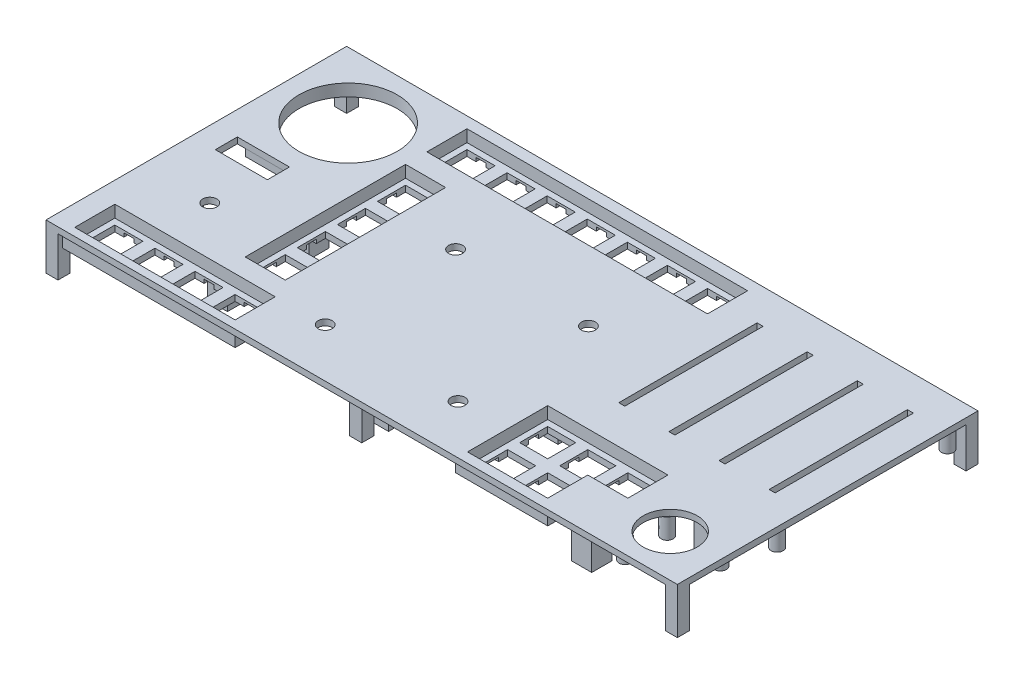
SolidWorks part; units mm, degrees
ref_plane "Front Plane" through (0, 0, 0) normal (0, 0, 1) x (1, 0, 0)
ref_plane "Top Plane" through (0, 0, 0) normal (0, 1, 0) x (1, 0, 0)
ref_plane "Right Plane" through (0, 0, 0) normal (1, 0, 0) x (0, 0, -1)
sketch "Sketch1" plane through (0, 0, 0) normal (0, 1, 0) x (1, 0, 0)
  line L1 (0, 0) -> (315, 0)
  line L2 (0, 0) -> (0, 150)
  line L3 (0, 150) -> (315, 150)
  line L4 (315, 0) -> (315, 150)
  line L5 (157.5, 150) -> (157.5, 0) construction
  line L6 (0, 75) -> (315, 75) construction
  line L7 (11.8793, 83.5932) -> (37.8793, 83.5932)
  line L8 (11.8793, 83.5932) -> (11.8793, 72.5932)
  line L9 (11.8793, 72.5932) -> (37.8793, 72.5932)
  line L10 (37.8793, 83.5932) -> (37.8793, 72.5932)
  line L11 (24.8793, 72.5932) -> (24.8793, 83.5932) construction
  line L12 (11.8793, 78.0932) -> (37.8793, 78.0932) construction
  line L17 (114.9071, 89.45) -> (181.1755, 89.45) construction
  line L18 (65.6251, 144.4154) -> (205.6251, 144.4154)
  line L42 (260.2509, 144.4154) -> (285.2509, 144.4154)
  line L43 (234.1707, 144.4154) -> (259.1707, 144.4154)
  line L44 (234.1707, 144.4154) -> (234.1707, 52.4154)
  line L45 (234.1707, 52.4154) -> (259.1707, 52.4154)
  line L46 (259.1707, 144.4154) -> (259.1707, 52.4154)
  line L47 (246.6707, 52.4154) -> (246.6707, 144.4154) construction
  line L48 (234.1707, 98.4154) -> (259.1707, 98.4154) construction
  line L49 (260.2509, 144.4154) -> (260.2509, 52.4154)
  line L50 (260.2509, 52.4154) -> (285.2509, 52.4154)
  line L51 (285.2509, 144.4154) -> (285.2509, 52.4154)
  line L52 (287.1734, 144.4154) -> (312.1734, 144.4154)
  line L53 (287.1734, 144.4154) -> (287.1734, 52.4154)
  line L54 (287.1734, 52.4154) -> (312.1734, 52.4154)
  line L55 (312.1734, 144.4154) -> (312.1734, 52.4154)
  line L72 (65.6251, 144.4154) -> (65.6251, 124.4154)
  line L73 (65.6251, 124.4154) -> (205.6251, 124.4154)
  line L74 (205.6251, 144.4154) -> (205.6251, 124.4154)
  line L75 (135.6251, 124.4154) -> (135.6251, 144.4154) construction
  line L76 (65.6251, 134.4154) -> (205.6251, 134.4154) construction
  line L81 (65.688, 113.6965) -> (85.688, 113.6965)
  line L82 (65.688, 113.6965) -> (65.688, 33.6965)
  line L83 (10.3843, 23.9694) -> (90.3843, 23.9694)
  line L84 (10.3843, 23.9694) -> (10.3843, 3.9694)
  line L85 (10.3843, 3.9694) -> (90.3843, 3.9694)
  line L86 (90.3843, 23.9694) -> (90.3843, 3.9694)
  line L87 (50.3843, 3.9694) -> (50.3843, 23.9694) construction
  line L88 (10.3843, 13.9694) -> (90.3843, 13.9694) construction
  line L89 (65.688, 33.6965) -> (85.688, 33.6965)
  line L90 (85.688, 113.6965) -> (85.688, 33.6965)
  line L91 (75.688, 33.6965) -> (75.688, 113.6965) construction
  line L92 (65.688, 73.6965) -> (85.688, 73.6965) construction
  line L93 (205.3895, 44.9232) -> (245.3895, 44.9232)
  line L94 (205.3895, 44.9232) -> (205.3895, 4.9232)
  line L95 (205.3895, 4.9232) -> (245.3895, 4.9232)
  line L96 (245.3895, 44.9232) -> (245.3895, 4.9232)
  line L97 (225.3895, 4.9232) -> (225.3895, 44.9232) construction
  line L98 (205.3895, 24.9232) -> (245.3895, 24.9232) construction
  line L99 (245.3895, 44.9232) -> (265.3895, 44.9232)
  line L100 (245.3895, 44.9232) -> (245.3895, 24.9232)
  line L101 (245.3895, 24.9232) -> (265.3895, 24.9232)
  line L102 (265.3895, 44.9232) -> (265.3895, 24.9232)
  line L103 (255.3895, 24.9232) -> (255.3895, 44.9232) construction
  line L104 (245.3895, 34.9232) -> (265.3895, 34.9232) construction
  line L105 (181.1755, 89.45) -> (181.1755, 24.3783) construction
  line L106 (181.1755, 24.3783) -> (114.9071, 24.3783) construction
  line L107 (33.5208, 117.195) -> (33.5208, 48.1962) construction
  line L109 (273.3018, 34.1392) -> (307.3018, 34.1392)
  line L110 (273.3018, 34.1392) -> (273.3018, 8.1392)
  line L111 (273.3018, 8.1392) -> (307.3018, 8.1392)
  line L112 (307.3018, 34.1392) -> (307.3018, 8.1392)
  line L113 (290.3018, 8.1392) -> (290.3018, 34.1392) construction
  line L114 (273.3018, 21.1392) -> (307.3018, 21.1392) construction
  line L115 (117.5413, 65.9142) -> (178.5413, 65.9142)
  line L116 (117.5413, 65.9142) -> (117.5413, 47.9142)
  line L117 (117.5413, 47.9142) -> (178.5413, 47.9142)
  line L118 (178.5413, 65.9142) -> (178.5413, 47.9142)
  line L119 (148.0413, 47.9142) -> (148.0413, 65.9142) construction
  line L120 (117.5413, 56.9142) -> (178.5413, 56.9142) construction
  line L121 (5.8793, 85.7294) -> (45.8793, 85.7294)
  line L122 (5.8793, 85.7294) -> (5.8793, 70.457)
  line L123 (5.8793, 70.457) -> (45.8793, 70.457)
  line L124 (45.8793, 85.7294) -> (45.8793, 70.457)
  line L125 (25.8793, 70.457) -> (25.8793, 85.7294) construction
  line L126 (5.8793, 78.0932) -> (45.8793, 78.0932) construction
  circle A0 centre (33.5208, 117.195) radius 27.5
  circle A1 centre (33.5208, 48.1962) radius 20
  circle A2 centre (114.9071, 24.3783) radius 20
  circle A3 centre (114.9071, 89.45) radius 20
  circle A4 centre (181.1755, 24.3783) radius 20
  circle A5 centre (181.1755, 89.45) radius 20
  point P38 (148.0413, 56.9142)
  point P42 (148.0413, 89.45)
  point P56 (181.1755, 56.9142)
  point P57 (25.8793, 78.0932)
  point P195 (24.8793, 78.0932)
  point P224 (290.3018, 21.1392)
  point P252 (246.6707, 98.4154)
  point P259 (225.3895, 24.9232)
  point P417 (255.3895, 34.9232)
  point P438 (75.688, 73.6965)
  point P456 (157.5, 75)
  point P559 (50.3843, 13.9694)
  point P704 (135.6251, 134.4154)
  dimension "D3" = 55
  dimension "D6" = 40
  dimension "D1" = 150
  dimension "D2" = 315
  dimension "D4" = 26
  dimension "D5" = 11
  dimension "D7" = 20
  dimension "D8" = 140
  dimension "D9" = 25
  dimension "D10" = 92
  dimension "D11" = 20
  dimension "D12" = 80
  dimension "D13" = 20
  dimension "D14" = 80
  dimension "D15" = 40
  dimension "D16" = 40
  dimension "D17" = 20
  dimension "D18" = 34
  dimension "D19" = 26
  dimension "D20" = 61
  dimension "D21" = 18
  dimension "D22" = 6
  dimension "D23" = 8
  dimension "D24" = 25
  dimension "D25" = 25
sketch "Sketch2" plane through (0, 0, 0) normal (0, 1, 0) x (1, 0, 0)
  line L1 (0, 0) -> (315, 0)
  line L2 (0, 0) -> (0, 150)
  line L3 (0, 150) -> (315, 150)
  line L4 (315, 0) -> (315, 150)
  line L5 (157.5, 150) -> (157.5, 0) construction
  line L6 (0, 75) -> (315, 75) construction
  point P0 (157.5, 75)
extrude "Boss-Extrude1" add sketch "Sketch2" along normal blind 3
sketch "Sketch3" [suppressed] plane through (0, 0, 0) normal (0, 1, 0) x (1, 0, 0)
  line L0 (114.9071, 89.45) -> (114.9071, 81.45) construction
  line L1 (113.1571, 82.7) -> (116.6571, 82.7)
  line L2 (113.1571, 82.7) -> (113.1571, 80.2)
  line L3 (113.1571, 80.2) -> (116.6571, 80.2)
  line L4 (116.6571, 82.7) -> (116.6571, 80.2)
  line L5 (114.9071, 80.2) -> (114.9071, 82.7) construction
  line L6 (113.1571, 81.45) -> (116.6571, 81.45) construction
  line L7 (179.4255, 82.7) -> (182.9255, 82.7)
  line L8 (179.4255, 82.7) -> (179.4255, 80.2)
  line L9 (179.4255, 80.2) -> (182.9255, 80.2)
  line L10 (182.9255, 82.7) -> (182.9255, 80.2)
  line L11 (181.1755, 80.2) -> (181.1755, 82.7) construction
  line L12 (179.4255, 81.45) -> (182.9255, 81.45) construction
  line L13 (179.4255, 17.6283) -> (182.9255, 17.6283)
  line L14 (179.4255, 17.6283) -> (179.4255, 15.1283)
  line L15 (179.4255, 15.1283) -> (182.9255, 15.1283)
  line L16 (182.9255, 17.6283) -> (182.9255, 15.1283)
  line L17 (181.1755, 15.1283) -> (181.1755, 17.6283) construction
  line L18 (179.4255, 16.3783) -> (182.9255, 16.3783) construction
  line L19 (113.1571, 17.6283) -> (116.6571, 17.6283)
  line L20 (113.1571, 17.6283) -> (113.1571, 15.1283)
  line L21 (113.1571, 15.1283) -> (116.6571, 15.1283)
  line L22 (116.6571, 17.6283) -> (116.6571, 15.1283)
  line L23 (114.9071, 15.1283) -> (114.9071, 17.6283) construction
  line L24 (113.1571, 16.3783) -> (116.6571, 16.3783) construction
  line L25 (31.7708, 41.4462) -> (35.2708, 41.4462)
  line L26 (31.7708, 41.4462) -> (31.7708, 38.9462)
  line L27 (31.7708, 38.9462) -> (35.2708, 38.9462)
  line L28 (35.2708, 41.4462) -> (35.2708, 38.9462)
  line L29 (33.5208, 38.9462) -> (33.5208, 41.4462) construction
  line L30 (31.7708, 40.1962) -> (35.2708, 40.1962) construction
  line L31 (181.1755, 89.45) -> (181.1755, 82.7) construction
  line L32 (114.9071, 24.3783) -> (114.9071, 17.6283) construction
  line L33 (181.1755, 24.3783) -> (181.1755, 17.6283) construction
  line L34 (33.5208, 48.1962) -> (33.5208, 41.4462) construction
  circle A0 centre (114.9071, 89.45) radius 3.6
  circle A1 centre (181.1755, 89.45) radius 3.6
  circle A2 centre (181.1755, 24.3783) radius 3.6
  circle A3 centre (114.9071, 24.3783) radius 3.6
  circle A4 centre (33.5208, 48.1962) radius 3.6
  point P15 (114.9071, 81.45)
  point P19 (181.1755, 81.45)
  point P23 (181.1755, 16.3783)
  point P27 (114.9071, 16.3783)
  point P31 (33.5208, 40.1962)
  dimension "D1" = 7.2
  dimension "D2" = 8
  dimension "D3" = 8
  dimension "D4" = 8
  dimension "D5" = 8
  dimension "D6" = 3.5
  dimension "D7" = 2.5
  dimension "D8" = 8
extrude "rotatry_potentiameter_hole" [suppressed] cut sketch "Sketch3" along normal blind 3
sketch "Sketch4" [suppressed] plane through (0, 0, 0) normal (0, 1, 0) x (1, 0, 0)
  line L0 (114.9071, 12.8783) -> (114.9071, 14.8783)
  line L1 (114.9071, 33.8783) -> (114.9071, 35.8783)
  line L2 (181.1755, 12.8783) -> (181.1755, 14.8783)
  line L3 (181.1755, 33.8783) -> (181.1755, 35.8783)
  line L4 (114.9071, 79.95) -> (114.9071, 77.95)
  line L5 (114.9071, 100.95) -> (114.9071, 98.95)
  line L6 (114.9071, 24.3783) -> (114.9071, 89.45) construction
  line L7 (181.1755, 77.95) -> (181.1755, 79.95)
  line L8 (181.1755, 98.95) -> (181.1755, 100.95)
  line L9 (181.1755, 89.45) -> (181.1755, 24.3783) construction
  line L10 (33.5208, 36.6962) -> (33.5208, 38.6962)
  line L11 (33.5208, 57.6962) -> (33.5208, 59.6962)
  line L12 (33.5208, 117.195) -> (33.5208, 48.1962) construction
  arc A0 (114.9071, 14.8783) -> (114.9071, 33.8783) centre (114.9071, 24.3783) cw
  arc A1 (114.9071, 12.8783) -> (114.9071, 35.8783) centre (114.9071, 24.3783) cw
  arc A2 (181.1755, 14.8783) -> (181.1755, 33.8783) centre (181.1755, 24.3783) cw
  arc A3 (181.1755, 12.8783) -> (181.1755, 35.8783) centre (181.1755, 24.3783) cw
  arc A4 (114.9071, 77.95) -> (114.9071, 100.95) centre (114.9071, 89.45) cw
  arc A5 (114.9071, 79.95) -> (114.9071, 98.95) centre (114.9071, 89.45) cw
  arc A6 (181.1755, 79.95) -> (181.1755, 98.95) centre (181.1755, 89.45) cw
  arc A7 (181.1755, 77.95) -> (181.1755, 100.95) centre (181.1755, 89.45) cw
  arc A8 (33.5208, 38.6962) -> (33.5208, 57.6962) centre (33.5208, 48.1962) cw
  arc A9 (33.5208, 36.6962) -> (33.5208, 59.6962) centre (33.5208, 48.1962) cw
  dimension "D1" = 9.5
  dimension "D3" = 9.5
  dimension "D6" = 9.5
  dimension "D7" = 9.5
  dimension "D9" = 9.5
  dimension "D2" = 2
  dimension "D4" = 2
  dimension "D5" = 2
  dimension "D8" = 2
  dimension "D10" = 2
extrude "Boss-Extrude2" [suppressed] add sketch "Sketch4" against normal blind 5
sketch "Sketch28" plane through (0, 0, 0) normal (0, 1, 0) x (1, 0, 0)
  circle A0 centre (114.9071, 89.45) radius 3.5
  circle A1 centre (181.1755, 89.45) radius 3.5
  circle A2 centre (181.1755, 24.3783) radius 3.5
  circle A3 centre (114.9071, 24.3783) radius 3.5
  circle A4 centre (33.5208, 48.1962) radius 3.5
  dimension "D1" = 7
extrude "Cut-Extrude15" cut sketch "Sketch28" along normal blind 10
sketch "Sketch29" plane through (0, 0, 0) normal (0, 1, 0) x (1, 0, 0)
  line L0 (108.5671, 80.95) -> (125.5671, 80.95) construction
  line L1 (114.9071, 89.45) -> (114.9071, 80.95) construction
  line L2 (173.7538, 79.9853) -> (190.7538, 79.9853) construction
  line L3 (123.0671, 83.45) -> (128.0671, 83.45)
  line L4 (123.0671, 83.45) -> (123.0671, 78.45)
  line L5 (123.0671, 78.45) -> (128.0671, 78.45)
  line L6 (128.0671, 83.45) -> (128.0671, 78.45)
  line L7 (125.5671, 78.45) -> (125.5671, 83.45) construction
  line L8 (123.0671, 80.95) -> (128.0671, 80.95) construction
  line L9 (106.0671, 83.45) -> (111.0671, 83.45)
  line L10 (106.0671, 83.45) -> (106.0671, 78.45)
  line L11 (106.0671, 78.45) -> (111.0671, 78.45)
  line L12 (111.0671, 83.45) -> (111.0671, 78.45)
  line L13 (108.5671, 78.45) -> (108.5671, 83.45) construction
  line L14 (106.0671, 80.95) -> (111.0671, 80.95) construction
  line L15 (180.0938, 88.4853) -> (180.0938, 79.9853) construction
  line L16 (188.2538, 82.4853) -> (193.2538, 82.4853)
  line L17 (188.2538, 82.4853) -> (188.2538, 77.4853)
  line L18 (188.2538, 77.4853) -> (193.2538, 77.4853)
  line L19 (193.2538, 82.4853) -> (193.2538, 77.4853)
  line L20 (190.7538, 77.4853) -> (190.7538, 82.4853) construction
  line L21 (188.2538, 79.9853) -> (193.2538, 79.9853) construction
  line L22 (171.2538, 82.4853) -> (176.2538, 82.4853)
  line L23 (171.2538, 82.4853) -> (171.2538, 77.4853)
  line L24 (171.2538, 77.4853) -> (176.2538, 77.4853)
  line L25 (176.2538, 82.4853) -> (176.2538, 77.4853)
  line L26 (173.7538, 77.4853) -> (173.7538, 82.4853) construction
  line L27 (171.2538, 79.9853) -> (176.2538, 79.9853) construction
  line L28 (174.8355, 15.8783) -> (191.8355, 15.8783) construction
  line L29 (181.1755, 24.3783) -> (181.1755, 15.8783) construction
  line L30 (189.3355, 18.3783) -> (194.3355, 18.3783)
  line L31 (189.3355, 18.3783) -> (189.3355, 13.3783)
  line L32 (189.3355, 13.3783) -> (194.3355, 13.3783)
  line L33 (194.3355, 18.3783) -> (194.3355, 13.3783)
  line L34 (191.8355, 13.3783) -> (191.8355, 18.3783) construction
  line L35 (189.3355, 15.8783) -> (194.3355, 15.8783) construction
  line L36 (172.3355, 18.3783) -> (177.3355, 18.3783)
  line L37 (172.3355, 18.3783) -> (172.3355, 13.3783)
  line L38 (172.3355, 13.3783) -> (177.3355, 13.3783)
  line L39 (177.3355, 18.3783) -> (177.3355, 13.3783)
  line L40 (174.8355, 13.3783) -> (174.8355, 18.3783) construction
  line L41 (172.3355, 15.8783) -> (177.3355, 15.8783) construction
  line L42 (108.5671, 15.8783) -> (125.5671, 15.8783) construction
  line L43 (114.9071, 24.3783) -> (114.9071, 15.8783) construction
  line L44 (123.0671, 18.3783) -> (128.0671, 18.3783)
  line L45 (123.0671, 18.3783) -> (123.0671, 13.3783)
  line L46 (123.0671, 13.3783) -> (128.0671, 13.3783)
  line L47 (128.0671, 18.3783) -> (128.0671, 13.3783)
  line L48 (125.5671, 13.3783) -> (125.5671, 18.3783) construction
  line L49 (123.0671, 15.8783) -> (128.0671, 15.8783) construction
  line L50 (106.0671, 18.3783) -> (111.0671, 18.3783)
  line L51 (106.0671, 18.3783) -> (106.0671, 13.3783)
  line L52 (106.0671, 13.3783) -> (111.0671, 13.3783)
  line L53 (111.0671, 18.3783) -> (111.0671, 13.3783)
  line L54 (108.5671, 13.3783) -> (108.5671, 18.3783) construction
  line L55 (106.0671, 15.8783) -> (111.0671, 15.8783) construction
  line L56 (27.1808, 39.6962) -> (44.1808, 39.6962) construction
  line L57 (33.5208, 48.1962) -> (33.5208, 39.6962) construction
  line L58 (41.6808, 42.1962) -> (46.6808, 42.1962)
  line L59 (41.6808, 42.1962) -> (41.6808, 37.1962)
  line L60 (41.6808, 37.1962) -> (46.6808, 37.1962)
  line L61 (46.6808, 42.1962) -> (46.6808, 37.1962)
  line L62 (44.1808, 37.1962) -> (44.1808, 42.1962) construction
  line L63 (41.6808, 39.6962) -> (46.6808, 39.6962) construction
  line L64 (24.6808, 42.1962) -> (29.6808, 42.1962)
  line L65 (24.6808, 42.1962) -> (24.6808, 37.1962)
  line L66 (24.6808, 37.1962) -> (29.6808, 37.1962)
  line L67 (29.6808, 42.1962) -> (29.6808, 37.1962)
  line L68 (27.1808, 37.1962) -> (27.1808, 42.1962) construction
  line L69 (24.6808, 39.6962) -> (29.6808, 39.6962) construction
  circle A0 centre (108.5671, 80.95) radius 1.6
  circle A1 centre (125.5671, 80.95) radius 1.6
  circle A2 centre (173.7538, 79.9853) radius 1.6
  circle A3 centre (190.7538, 79.9853) radius 1.6
  circle A4 centre (174.8355, 15.8783) radius 1.6
  circle A5 centre (191.8355, 15.8783) radius 1.6
  circle A6 centre (108.5671, 15.8783) radius 1.6
  circle A7 centre (125.5671, 15.8783) radius 1.6
  circle A8 centre (27.1808, 39.6962) radius 1.6
  circle A9 centre (44.1808, 39.6962) radius 1.6
  dimension "D4" = 3.2
  dimension "D5" = 3.2
  dimension "D12" = 3.2
  dimension "D13" = 3.2
  dimension "D20" = 3.2
  dimension "D21" = 3.2
  dimension "D28" = 3.2
  dimension "D29" = 3.2
  dimension "D36" = 3.2
  dimension "D37" = 3.2
  dimension "D1" = 8.5
  dimension "D2" = 6.34
  dimension "D3" = 17
  dimension "D6" = 5
  dimension "D7" = 5
  dimension "D8" = 5
  dimension "D9" = 5
  dimension "D10" = 6.34
  dimension "D11" = 17
  dimension "D14" = 5
  dimension "D15" = 5
  dimension "D16" = 5
  dimension "D17" = 5
  dimension "D18" = 6.34
  dimension "D19" = 17
  dimension "D22" = 5
  dimension "D23" = 5
  dimension "D24" = 5
  dimension "D25" = 5
  dimension "D26" = 6.34
  dimension "D27" = 17
  dimension "D30" = 5
  dimension "D31" = 5
  dimension "D32" = 5
  dimension "D33" = 5
  dimension "D34" = 6.34
  dimension "D35" = 17
  dimension "D38" = 5
  dimension "D39" = 5
  dimension "D40" = 5
  dimension "D41" = 5
extrude "Boss-Extrude15" add sketch "Sketch29" against normal blind 6.5
ref_plane "Plane1" through (0, -6, 0) normal (0, 1, 0) x (1, 0, 0)
sketch "Sketch9" plane through (0, 0, 0) normal (0, 1, 0) x (1, 0, 0)
  line L5 (135.6251, 123.3949) -> (135.6251, 145.4359) construction
  line L6 (76.4108, 133.3949) -> (216.4108, 133.3949) construction
  line L11 (86.5676, 32.4942) -> (86.5676, 112.4942) construction
  line L12 (76.5676, 72.4942) -> (74.8083, 72.4942) construction
  line L17 (50.3843, 3.1287) -> (50.3843, 24.8101) construction
  line L18 (10.3843, 13.1287) -> (90.3843, 13.1287) construction
  line L24 (65.6251, 144.4154) -> (65.6251, 124.4154) construction
  line L25 (62.6251, 147.4154) -> (208.6251, 147.4154)
  line L26 (62.6251, 147.4154) -> (62.6251, 121.4154)
  line L27 (62.6251, 121.4154) -> (208.6251, 121.4154)
  line L28 (208.6251, 147.4154) -> (208.6251, 121.4154)
  line L29 (135.6251, 121.4154) -> (135.6251, 147.4154) construction
  line L30 (62.6251, 134.4154) -> (208.6251, 134.4154) construction
  line L31 (62.688, 116.6965) -> (88.688, 116.6965)
  line L32 (62.688, 116.6965) -> (62.688, 28.2919)
  line L33 (62.688, 28.2919) -> (88.688, 28.2919)
  line L34 (88.688, 116.6965) -> (88.688, 28.2919)
  line L35 (75.688, 28.2919) -> (75.688, 116.6965) construction
  line L36 (62.688, 72.4942) -> (88.688, 72.4942) construction
  line L37 (7.3843, 26.9694) -> (93.3843, 26.9694)
  line L38 (7.3843, 26.9694) -> (7.3843, 0.9694)
  line L39 (7.3843, 0.9694) -> (93.3843, 0.9694)
  line L40 (93.3843, 26.9694) -> (93.3843, 0.9694)
  line L41 (50.3843, 0.9694) -> (50.3843, 26.9694) construction
  line L42 (7.3843, 13.9694) -> (93.3843, 13.9694) construction
  line L43 (65.6251, 144.4154) -> (205.6251, 144.4154) construction
  line L44 (65.688, 113.6965) -> (85.688, 113.6965) construction
  line L45 (65.688, 113.6965) -> (65.688, 33.6965) construction
  line L46 (10.3843, 23.9694) -> (90.3843, 23.9694) construction
  line L47 (90.3843, 23.9694) -> (90.3843, 3.9694) construction
  line L48 (202.3895, 47.9232) -> (202.3895, 1.9232)
  line L49 (202.3895, 1.9232) -> (248.3895, 1.9232)
  line L50 (248.3895, 1.9232) -> (248.3895, 21.9232)
  line L51 (248.3895, 21.9232) -> (268.3895, 21.9232)
  line L52 (268.3895, 21.9232) -> (268.3895, 47.9232)
  line L53 (268.3895, 47.9232) -> (202.3895, 47.9232)
  line L54 (205.3895, 44.9232) -> (245.3895, 44.9232) construction
  line L55 (265.3895, 44.9232) -> (265.3895, 24.9232) construction
  line L56 (245.3895, 24.9232) -> (265.3895, 24.9232) construction
  line L57 (245.3895, 44.9232) -> (245.3895, 4.9232) construction
  line L58 (205.3895, 4.9232) -> (245.3895, 4.9232) construction
  line L59 (205.3895, 44.9232) -> (205.3895, 4.9232) construction
  line L60 (205.6251, 144.4154) -> (205.6251, 124.4154) construction
  line L61 (10.3843, 3.9694) -> (90.3843, 3.9694) construction
  line L62 (10.3843, 23.9694) -> (10.3843, 3.9694) construction
  line L64 (75.688, 33.6965) -> (75.688, 113.6965) construction
  line L65 (65.6251, 134.4154) -> (205.6251, 134.4154) construction
  point P0 (135.6251, 134.4154)
  point P4 (75.688, 72.4942)
  point P8 (50.3843, 13.9694)
  point P260 (135.6251, 133.3949)
  point P267 (86.5676, 72.4942)
  point P286 (50.3843, 13.1287)
  dimension "D1" = 3
  dimension "D2" = 3
  dimension "D3" = 3
  dimension "D4" = 3
  dimension "D5" = 3
  dimension "D6" = 3
  dimension "D7" = 3
  dimension "D8" = 3
  dimension "D9" = 3
  dimension "D10" = 3
  dimension "D11" = 3
  dimension "D12" = 3
  dimension "D13" = 3
  dimension "D14" = 3
  dimension "D15" = 3
extrude "Boss-Extrude5" add sketch "Sketch9" against normal blind 6
sketch "Sketch11" plane through (0, 0, 0) normal (0, 1, 0) x (1, 0, 0)
  line L0 (205.3895, 44.9232) -> (205.3895, 4.9232)
  line L1 (65.6251, 124.4154) -> (205.6251, 124.4154)
  line L2 (65.6251, 124.4154) -> (65.6251, 144.4154)
  line L3 (65.6251, 144.4154) -> (205.6251, 144.4154)
  line L4 (205.6251, 124.4154) -> (205.6251, 144.4154)
  line L5 (135.6251, 144.4154) -> (135.6251, 124.4154) construction
  line L6 (65.6251, 134.4154) -> (205.6251, 134.4154) construction
  line L7 (85.688, 113.6965) -> (65.688, 113.6965)
  line L8 (85.688, 113.6965) -> (85.688, 33.6965)
  line L9 (85.688, 33.6965) -> (65.688, 33.6965)
  line L10 (65.688, 113.6965) -> (65.688, 33.6965)
  line L11 (75.688, 33.6965) -> (75.688, 113.6965) construction
  line L12 (85.688, 73.6965) -> (65.688, 73.6965) construction
  line L13 (90.3843, 23.9694) -> (10.3843, 23.9694)
  line L14 (90.3843, 23.9694) -> (90.3843, 3.9694)
  line L15 (90.3843, 3.9694) -> (10.3843, 3.9694)
  line L16 (10.3843, 23.9694) -> (10.3843, 3.9694)
  line L17 (50.3843, 3.9694) -> (50.3843, 23.9694) construction
  line L18 (90.3843, 13.9694) -> (10.3843, 13.9694) construction
  line L19 (205.3895, 4.9232) -> (245.3895, 4.9232)
  line L20 (245.3895, 4.9232) -> (245.3895, 24.9232)
  line L21 (245.3895, 24.9232) -> (265.3895, 24.9232)
  line L22 (265.3895, 24.9232) -> (265.3895, 44.9232)
  line L23 (265.3895, 44.9232) -> (205.3895, 44.9232)
  point P204 (50.3843, 13.9694)
  point P232 (75.688, 73.6965)
  point P312 (135.6251, 134.4154)
extrude "Cut-Extrude8" cut sketch "Sketch11" along normal blind 3 and the other way blind 3
sketch "Sketch5" plane through (0, 0, 0) normal (0, 1, 0) x (1, 0, 0)
  line L0 (65.6251, 134.4154) -> (205.6251, 134.4154) construction
  line L1 (68.6251, 141.4154) -> (82.6251, 141.4154)
  line L2 (68.6251, 141.4154) -> (68.6251, 127.4154)
  line L3 (68.6251, 127.4154) -> (82.6251, 127.4154)
  line L4 (82.6251, 141.4154) -> (82.6251, 127.4154)
  line L5 (75.6251, 127.4154) -> (75.6251, 141.4154) construction
  line L6 (68.6251, 134.4154) -> (82.6251, 134.4154) construction
  line L7 (65.6251, 144.4154) -> (65.6251, 124.4154) construction
  line L8 (65.6251, 144.4154) -> (205.6251, 144.4154) construction
  line L9 (102.6251, 141.4154) -> (102.6251, 127.4154)
  line L10 (88.6251, 127.4154) -> (102.6251, 127.4154)
  line L11 (88.6251, 141.4154) -> (88.6251, 127.4154)
  line L12 (88.6251, 141.4154) -> (102.6251, 141.4154)
  line L13 (122.6251, 141.4154) -> (122.6251, 127.4154)
  line L14 (108.6251, 127.4154) -> (122.6251, 127.4154)
  line L15 (108.6251, 141.4154) -> (108.6251, 127.4154)
  line L16 (108.6251, 141.4154) -> (122.6251, 141.4154)
  line L17 (142.6251, 141.4154) -> (142.6251, 127.4154)
  line L18 (128.6251, 127.4154) -> (142.6251, 127.4154)
  line L19 (128.6251, 141.4154) -> (128.6251, 127.4154)
  line L20 (128.6251, 141.4154) -> (142.6251, 141.4154)
  line L21 (162.6251, 141.4154) -> (162.6251, 127.4154)
  line L22 (148.6251, 127.4154) -> (162.6251, 127.4154)
  line L23 (148.6251, 141.4154) -> (148.6251, 127.4154)
  line L24 (148.6251, 141.4154) -> (162.6251, 141.4154)
  line L25 (182.6251, 141.4154) -> (182.6251, 127.4154)
  line L26 (168.6251, 127.4154) -> (182.6251, 127.4154)
  line L27 (168.6251, 141.4154) -> (168.6251, 127.4154)
  line L28 (168.6251, 141.4154) -> (182.6251, 141.4154)
  line L29 (202.6251, 141.4154) -> (202.6251, 127.4154)
  line L30 (188.6251, 127.4154) -> (202.6251, 127.4154)
  line L31 (188.6251, 141.4154) -> (188.6251, 127.4154)
  line L32 (188.6251, 141.4154) -> (202.6251, 141.4154)
  line L33 (75.688, 33.6965) -> (75.688, 113.6965) construction
  line L34 (68.688, 110.6965) -> (82.688, 110.6965)
  line L35 (68.688, 110.6965) -> (68.688, 96.6965)
  line L36 (68.688, 96.6965) -> (82.688, 96.6965)
  line L37 (82.688, 110.6965) -> (82.688, 96.6965)
  line L38 (75.688, 96.6965) -> (75.688, 110.6965) construction
  line L39 (68.688, 103.6965) -> (82.688, 103.6965) construction
  line L40 (65.688, 113.6965) -> (85.688, 113.6965) construction
  line L41 (85.688, 113.6965) -> (85.688, 33.6965) construction
  line L42 (82.688, 90.6965) -> (82.688, 76.6965)
  line L43 (68.688, 76.6965) -> (82.688, 76.6965)
  line L44 (68.688, 90.6965) -> (68.688, 76.6965)
  line L45 (68.688, 90.6965) -> (82.688, 90.6965)
  line L46 (82.688, 70.6965) -> (82.688, 56.6965)
  line L47 (68.688, 56.6965) -> (82.688, 56.6965)
  line L48 (68.688, 70.6965) -> (68.688, 56.6965)
  line L49 (68.688, 70.6965) -> (82.688, 70.6965)
  line L50 (82.688, 50.6965) -> (82.688, 36.6965)
  line L51 (68.688, 36.6965) -> (82.688, 36.6965)
  line L52 (68.688, 50.6965) -> (68.688, 36.6965)
  line L53 (68.688, 50.6965) -> (82.688, 50.6965)
  line L54 (10.3843, 13.9694) -> (90.3843, 13.9694) construction
  line L55 (13.3843, 20.9694) -> (27.3843, 20.9694)
  line L56 (13.3843, 20.9694) -> (13.3843, 6.9694)
  line L57 (13.3843, 6.9694) -> (27.3843, 6.9694)
  line L58 (27.3843, 20.9694) -> (27.3843, 6.9694)
  line L59 (20.3843, 6.9694) -> (20.3843, 20.9694) construction
  line L60 (13.3843, 13.9694) -> (27.3843, 13.9694) construction
  line L61 (10.3843, 23.9694) -> (10.3843, 3.9694) construction
  line L62 (10.3843, 23.9694) -> (90.3843, 23.9694) construction
  line L63 (33.3843, 20.9694) -> (47.3843, 20.9694)
  line L64 (47.3843, 20.9694) -> (47.3843, 6.9694)
  line L65 (33.3843, 6.9694) -> (47.3843, 6.9694)
  line L66 (33.3843, 20.9694) -> (33.3843, 6.9694)
  line L67 (53.3843, 20.9694) -> (67.3843, 20.9694)
  line L68 (67.3843, 20.9694) -> (67.3843, 6.9694)
  line L69 (53.3843, 6.9694) -> (67.3843, 6.9694)
  line L70 (53.3843, 20.9694) -> (53.3843, 6.9694)
  line L71 (73.3843, 20.9694) -> (87.3843, 20.9694)
  line L72 (87.3843, 20.9694) -> (87.3843, 6.9694)
  line L73 (73.3843, 6.9694) -> (87.3843, 6.9694)
  line L74 (73.3843, 20.9694) -> (73.3843, 6.9694)
  line L75 (265.3895, 44.9232) -> (265.3895, 24.9232) construction
  line L76 (248.3895, 41.9232) -> (262.3895, 41.9232)
  line L77 (248.3895, 41.9232) -> (248.3895, 27.9232)
  line L78 (248.3895, 27.9232) -> (262.3895, 27.9232)
  line L79 (262.3895, 41.9232) -> (262.3895, 27.9232)
  line L80 (255.3895, 27.9232) -> (255.3895, 41.9232) construction
  line L81 (248.3895, 34.9232) -> (262.3895, 34.9232) construction
  line L82 (245.3895, 44.9232) -> (265.3895, 44.9232) construction
  line L83 (228.3895, 41.9232) -> (242.3895, 41.9232)
  line L84 (242.3895, 41.9232) -> (242.3895, 27.9232)
  line L85 (228.3895, 27.9232) -> (242.3895, 27.9232)
  line L86 (228.3895, 41.9232) -> (228.3895, 27.9232)
  line L87 (208.3895, 41.9232) -> (222.3895, 41.9232)
  line L88 (222.3895, 41.9232) -> (222.3895, 27.9232)
  line L89 (208.3895, 27.9232) -> (222.3895, 27.9232)
  line L90 (208.3895, 41.9232) -> (208.3895, 27.9232)
  line L91 (208.3895, 21.9232) -> (222.3895, 21.9232)
  line L92 (222.3895, 21.9232) -> (222.3895, 7.9232)
  line L93 (208.3895, 7.9232) -> (222.3895, 7.9232)
  line L94 (208.3895, 21.9232) -> (208.3895, 7.9232)
  line L95 (228.3895, 21.9232) -> (242.3895, 21.9232)
  line L96 (242.3895, 21.9232) -> (242.3895, 7.9232)
  line L97 (228.3895, 7.9232) -> (242.3895, 7.9232)
  line L98 (228.3895, 21.9232) -> (228.3895, 7.9232)
  point P0 (75.6251, 134.4154)
  point P10 (75.688, 103.6965)
  point P44 (20.3843, 13.9694)
  point P66 (255.3895, 34.9232)
  dimension "D1" = 3
  dimension "D2" = 3
  dimension "D3" = 14
  dimension "D5" = 3
  dimension "D6" = 3
  dimension "D7" = 14
  dimension "D9" = 3
  dimension "D10" = 3
  dimension "D11" = 14
  dimension "D13" = 3
  dimension "D14" = 3
  dimension "D4" = 7
  dimension "D8" = 4
  dimension "D12" = 4
  dimension "D15" = 3
  dimension "D16" = 2
extrude "Cut-Extrude3" cut sketch "Sketch5" along normal mid plane 20
sketch "Sketch6" plane through (0, -6, 0) normal (0, 1, 0) x (1, 0, 0)
  line L0 (10.3843, 13.9694) -> (90.3843, 13.9694) construction
  line L1 (17.8843, 23.9694) -> (22.8843, 23.9694)
  line L2 (17.8843, 23.9694) -> (17.8843, 3.9694)
  line L3 (17.8843, 3.9694) -> (22.8843, 3.9694)
  line L4 (22.8843, 23.9694) -> (22.8843, 3.9694)
  line L5 (20.3843, 3.9694) -> (20.3843, 23.9694) construction
  line L6 (17.8843, 13.9694) -> (22.8843, 13.9694) construction
  line L7 (10.3843, 3.9694) -> (90.3843, 3.9694) construction
  line L8 (265.3895, 44.9232) -> (265.3895, 24.9232) construction
  line L10 (42.8843, 23.9694) -> (42.8843, 3.9694)
  line L11 (37.8843, 3.9694) -> (42.8843, 3.9694)
  line L12 (37.8843, 23.9694) -> (37.8843, 3.9694)
  line L13 (37.8843, 23.9694) -> (42.8843, 23.9694)
  line L14 (62.8843, 23.9694) -> (62.8843, 3.9694)
  line L15 (57.8843, 3.9694) -> (62.8843, 3.9694)
  line L16 (57.8843, 23.9694) -> (57.8843, 3.9694)
  line L17 (57.8843, 23.9694) -> (62.8843, 23.9694)
  line L18 (82.8843, 23.9694) -> (82.8843, 3.9694)
  line L19 (77.8843, 3.9694) -> (82.8843, 3.9694)
  line L20 (77.8843, 23.9694) -> (77.8843, 3.9694)
  line L21 (77.8843, 23.9694) -> (82.8843, 23.9694)
  line L22 (73.1251, 144.4154) -> (78.1251, 144.4154)
  line L23 (73.1251, 144.4154) -> (73.1251, 124.4154)
  line L24 (73.1251, 124.4154) -> (78.1251, 124.4154)
  line L25 (78.1251, 144.4154) -> (78.1251, 124.4154)
  line L26 (65.6251, 144.4154) -> (205.6251, 144.4154) construction
  line L27 (65.6251, 124.4154) -> (205.6251, 124.4154) construction
  line L28 (68.6251, 127.4154) -> (68.6251, 141.4154) construction
  line L29 (98.1251, 144.4154) -> (98.1251, 124.4154)
  line L30 (93.1251, 124.4154) -> (98.1251, 124.4154)
  line L31 (93.1251, 144.4154) -> (93.1251, 124.4154)
  line L32 (93.1251, 144.4154) -> (98.1251, 144.4154)
  line L33 (118.1251, 144.4154) -> (118.1251, 124.4154)
  line L34 (113.1251, 124.4154) -> (118.1251, 124.4154)
  line L35 (113.1251, 144.4154) -> (113.1251, 124.4154)
  line L36 (113.1251, 144.4154) -> (118.1251, 144.4154)
  line L37 (138.1251, 144.4154) -> (138.1251, 124.4154)
  line L38 (133.1251, 124.4154) -> (138.1251, 124.4154)
  line L39 (133.1251, 144.4154) -> (133.1251, 124.4154)
  line L40 (133.1251, 144.4154) -> (138.1251, 144.4154)
  line L41 (158.1251, 144.4154) -> (158.1251, 124.4154)
  line L42 (153.1251, 124.4154) -> (158.1251, 124.4154)
  line L43 (153.1251, 144.4154) -> (153.1251, 124.4154)
  line L44 (153.1251, 144.4154) -> (158.1251, 144.4154)
  line L45 (178.1251, 144.4154) -> (178.1251, 124.4154)
  line L46 (173.1251, 124.4154) -> (178.1251, 124.4154)
  line L47 (173.1251, 144.4154) -> (173.1251, 124.4154)
  line L48 (173.1251, 144.4154) -> (178.1251, 144.4154)
  line L49 (198.1251, 144.4154) -> (198.1251, 124.4154)
  line L50 (193.1251, 124.4154) -> (198.1251, 124.4154)
  line L51 (193.1251, 144.4154) -> (193.1251, 124.4154)
  line L52 (193.1251, 144.4154) -> (198.1251, 144.4154)
  line L53 (75.688, 33.6965) -> (75.688, 113.6965) construction
  line L54 (65.688, 106.1965) -> (85.688, 106.1965)
  line L55 (65.688, 106.1965) -> (65.688, 101.1965)
  line L56 (65.688, 101.1965) -> (85.688, 101.1965)
  line L57 (85.688, 106.1965) -> (85.688, 101.1965)
  line L58 (75.688, 101.1965) -> (75.688, 106.1965) construction
  line L59 (65.688, 103.6965) -> (85.688, 103.6965) construction
  line L60 (85.688, 113.6965) -> (85.688, 33.6965) construction
  line L61 (13.3843, 6.9694) -> (13.3843, 20.9694) construction
  line L62 (65.688, 86.1965) -> (85.688, 86.1965)
  line L63 (85.688, 86.1965) -> (85.688, 81.1965)
  line L64 (65.688, 81.1965) -> (85.688, 81.1965)
  line L65 (65.688, 86.1965) -> (65.688, 81.1965)
  line L66 (65.688, 66.1965) -> (85.688, 66.1965)
  line L67 (85.688, 66.1965) -> (85.688, 61.1965)
  line L68 (65.688, 61.1965) -> (85.688, 61.1965)
  line L69 (65.688, 66.1965) -> (65.688, 61.1965)
  line L70 (65.688, 46.1965) -> (85.688, 46.1965)
  line L71 (85.688, 46.1965) -> (85.688, 41.1965)
  line L72 (65.688, 41.1965) -> (85.688, 41.1965)
  line L73 (65.688, 46.1965) -> (65.688, 41.1965)
  line L74 (265.3895, 37.4232) -> (205.3895, 37.4232)
  line L75 (265.3895, 37.4232) -> (265.3895, 32.4232)
  line L76 (265.3895, 32.4232) -> (205.3895, 32.4232)
  line L77 (205.3895, 37.4232) -> (205.3895, 32.4232)
  line L78 (235.3895, 32.4232) -> (235.3895, 37.4232) construction
  line L79 (265.3895, 34.9232) -> (205.3895, 34.9232) construction
  line L80 (205.3895, 44.9232) -> (205.3895, 4.9232) construction
  line L81 (245.3895, 34.9232) -> (265.3895, 34.9232) construction
  line L82 (245.3895, 44.9232) -> (245.3895, 4.9232) construction
  line L83 (245.3895, 17.4232) -> (205.3895, 17.4232)
  line L84 (245.3895, 17.4232) -> (245.3895, 12.4232)
  line L85 (245.3895, 12.4232) -> (205.3895, 12.4232)
  line L86 (205.3895, 17.4232) -> (205.3895, 12.4232)
  line L87 (225.3895, 12.4232) -> (225.3895, 17.4232) construction
  line L88 (245.3895, 14.9232) -> (205.3895, 14.9232) construction
  line L89 (82.688, 36.6965) -> (68.688, 36.6965) construction
  line L90 (222.3895, 7.9232) -> (208.3895, 7.9232) construction
  point P0 (20.3843, 13.9694)
  point P32 (75.688, 103.6965)
  point P414 (225.3895, 14.9232)
  point P420 (235.3895, 34.9232)
  dimension "D1" = 5
  dimension "D2" = 4.5
  dimension "D4" = 5
  dimension "D5" = 4.5
  dimension "D7" = 5
  dimension "D8" = 4.5
  dimension "D10" = 5
  dimension "D11" = 4.5
  dimension "D12" = 5
  dimension "D3" = 4
  dimension "D6" = 7
  dimension "D9" = 4
extrude "Cut-Extrude4" cut sketch "Sketch6" along normal blind 1.9
sketch "Sketch7" plane through (0, 0, 0) normal (0, 1, 0) x (1, 0, 0)
  line L0 (234.1707, 98.4154) -> (259.1707, 98.4154) construction
  line L1 (218.3645, 140.9154) -> (233.8645, 140.9154) construction
  line L2 (218.3645, 140.9154) -> (218.3645, 55.9154) construction
  line L3 (218.3645, 55.9154) -> (233.8645, 55.9154) construction
  line L4 (233.8645, 140.9154) -> (233.8645, 55.9154) construction
  line L5 (226.1145, 55.9154) -> (226.1145, 140.9154) construction
  line L6 (218.3645, 98.4154) -> (233.8645, 98.4154) construction
  line L7 (258.8645, 140.9154) -> (258.8645, 55.9154) construction
  line L8 (221.8645, 63.9154) -> (224.8645, 63.9154)
  line L9 (221.8645, 63.9154) -> (221.8645, 132.9154)
  line L10 (221.8645, 132.9154) -> (224.8645, 132.9154)
  line L11 (224.8645, 63.9154) -> (224.8645, 132.9154)
  line L12 (223.3645, 132.9154) -> (223.3645, 63.9154) construction
  line L13 (221.8645, 98.4154) -> (224.8645, 98.4154) construction
  line L14 (243.3645, 55.9154) -> (258.8645, 55.9154) construction
  line L15 (243.3645, 140.9154) -> (243.3645, 55.9154) construction
  line L16 (243.3645, 140.9154) -> (258.8645, 140.9154) construction
  line L17 (249.8645, 63.9154) -> (249.8645, 132.9154)
  line L18 (246.8645, 132.9154) -> (249.8645, 132.9154)
  line L19 (246.8645, 63.9154) -> (246.8645, 132.9154)
  line L20 (246.8645, 63.9154) -> (249.8645, 63.9154)
  line L21 (283.8645, 140.9154) -> (283.8645, 55.9154) construction
  line L22 (268.3645, 55.9154) -> (283.8645, 55.9154) construction
  line L23 (268.3645, 140.9154) -> (268.3645, 55.9154) construction
  line L24 (268.3645, 140.9154) -> (283.8645, 140.9154) construction
  line L25 (274.8645, 63.9154) -> (274.8645, 132.9154)
  line L26 (271.8645, 132.9154) -> (274.8645, 132.9154)
  line L27 (271.8645, 63.9154) -> (271.8645, 132.9154)
  line L28 (271.8645, 63.9154) -> (274.8645, 63.9154)
  line L29 (308.8645, 140.9154) -> (308.8645, 55.9154) construction
  line L30 (293.3645, 55.9154) -> (308.8645, 55.9154) construction
  line L31 (293.3645, 140.9154) -> (293.3645, 55.9154) construction
  line L32 (293.3645, 140.9154) -> (308.8645, 140.9154) construction
  line L33 (299.8645, 63.9154) -> (299.8645, 132.9154)
  line L34 (296.8645, 132.9154) -> (299.8645, 132.9154)
  line L35 (296.8645, 63.9154) -> (296.8645, 132.9154)
  line L36 (296.8645, 63.9154) -> (299.8645, 63.9154)
  point P0 (226.1145, 98.4154)
  point P6 (223.3645, 98.4154)
  dimension "D1" = 15.5
  dimension "D2" = 85
  dimension "D3" = 3
  dimension "D4" = 69
  dimension "D5" = 5
  dimension "D6" = 4
sketch "Sketch8" plane through (0, 0, 0) normal (0, 1, 0) x (1, 0, 0)
  circle A0 centre (218.3645, 140.9154) radius 1.6
  circle A1 centre (233.8645, 140.9154) radius 1.6
  circle A2 centre (218.3645, 55.9154) radius 1.6
  circle A3 centre (233.8645, 55.9154) radius 1.6
  circle A4 centre (243.3645, 55.9154) radius 1.6
  circle A5 centre (258.8645, 55.9154) radius 1.6
  circle A6 centre (268.3645, 55.9154) radius 1.6
  circle A7 centre (283.8645, 55.9154) radius 1.6
  circle A8 centre (283.8645, 140.9154) radius 1.6
  circle A9 centre (268.3645, 140.9154) radius 1.6
  circle A10 centre (258.8645, 140.9154) radius 1.6
  circle A11 centre (243.3645, 140.9154) radius 1.6
  circle A12 centre (308.8645, 140.9154) radius 1.6
  circle A13 centre (293.3645, 140.9154) radius 1.6
  circle A14 centre (293.3645, 55.9154) radius 1.6
  circle A15 centre (308.8645, 55.9154) radius 1.6
  circle A16 centre (218.3645, 140.9154) radius 3
  circle A17 centre (233.8645, 140.9154) radius 3
  circle A18 centre (243.3645, 140.9154) radius 3
  circle A19 centre (258.8645, 140.9154) radius 3
  circle A20 centre (268.3645, 140.9154) radius 3
  circle A21 centre (283.8645, 140.9154) radius 3
  circle A22 centre (293.3645, 140.9154) radius 3
  circle A23 centre (308.8645, 140.9154) radius 3
  circle A24 centre (308.8645, 55.9154) radius 3
  circle A25 centre (293.3645, 55.9154) radius 3
  circle A26 centre (283.8645, 55.9154) radius 3
  circle A27 centre (268.3645, 55.9154) radius 3
  circle A28 centre (258.8645, 55.9154) radius 3
  circle A29 centre (243.3645, 55.9154) radius 3
  circle A30 centre (233.8645, 55.9154) radius 3
  circle A31 centre (218.3645, 55.9154) radius 3
  dimension "D1" = 3.2
extrude "Cut-Extrude5" cut sketch "Sketch7" along normal blind 3
extrude "Boss-Extrude3" add sketch "Sketch8" against normal blind 12
sketch "Sketch13" plane through (0, 0, 0) normal (0, 1, 0) x (1, 0, 0)
  line L1 (11.8793, 83.5932) -> (37.8793, 83.5932)
  line L2 (11.8793, 83.5932) -> (11.8793, 72.5932)
  line L3 (11.8793, 72.5932) -> (37.8793, 72.5932)
  line L4 (37.8793, 83.5932) -> (37.8793, 72.5932)
  line L5 (24.8793, 72.5932) -> (24.8793, 83.5932) construction
  line L6 (11.8793, 78.0932) -> (37.8793, 78.0932) construction
  point P156 (24.8793, 78.0932)
extrude "Cut-Extrude9" cut sketch "Sketch13" along normal blind 10
sketch "Sketch14" plane through (0, 0, 0) normal (0, 1, 0) x (1, 0, 0)
  line L1 (15.4738, 84.1108) -> (34.2924, 84.1108)
  line L2 (15.4738, 84.1108) -> (15.4738, 86.1108)
  line L3 (15.4738, 86.1108) -> (34.2924, 86.1108)
  line L4 (34.2924, 84.1108) -> (34.2924, 86.1108)
  line L5 (24.8831, 86.1108) -> (24.8831, 84.1108) construction
  line L6 (15.4738, 85.1108) -> (34.2924, 85.1108) construction
  line L7 (15.4738, 72.1108) -> (34.2924, 72.1108)
  line L8 (15.4738, 72.1108) -> (15.4738, 70.1108)
  line L9 (15.4738, 70.1108) -> (34.2924, 70.1108)
  line L10 (34.2924, 72.1108) -> (34.2924, 70.1108)
  line L11 (24.8831, 70.1108) -> (24.8831, 72.1108) construction
  line L12 (15.4738, 71.1108) -> (34.2924, 71.1108) construction
  point P144 (24.8831, 71.1108)
  point P252 (24.8831, 85.1108)
  dimension "D1" = 12
  dimension "D2" = 2
  dimension "D3" = 2
extrude "Boss-Extrude7" add sketch "Sketch14" against normal blind 4
sketch "Sketch25" plane through (0, 0, 0) normal (0, 1, 0) x (1, 0, 0)
  circle A0 centre (33.5208, 117.195) radius 24.5
  dimension "D1" = 49
extrude "Cut-Extrude13" cut sketch "Sketch25" along normal blind 3
sketch "Sketch26" plane through (0, 0, 0) normal (0, -1, 0) x (1, 0, 0)
  line L0 (33.5208, -88.195) -> (33.5208, -93.195) construction
  circle A0 centre (33.5208, -117.195) radius 29
  circle A1 centre (33.5208, -117.195) radius 24
  circle A2 centre (33.5208, -90.695) radius 1.6
  circle A3 centre (56.4705, -130.445) radius 1.6
  circle A4 centre (33.5208, -117.195) radius 24
  circle A5 centre (10.5711, -130.445) radius 1.6
  circle A6 centre (33.5208, -117.195) radius 24
  dimension "D1" = 48
  dimension "D2" = 5
  dimension "D3" = 3.2
  dimension "D4" = 3
extrude "Boss-Extrude14" add sketch "Sketch26" along normal blind 3 contours A0 A2 A1 A5 A3 region at (5.3411, 0, -117.195)
sketch "Sketch27" plane through (0, -3, 0) normal (0, -1, 0) x (1, 0, 0)
  circle A0 centre (33.5208, -117.195) radius 24.5
  dimension "D1" = 49
extrude "Cut-Extrude14" cut sketch "Sketch27" against normal blind 10
sketch "Sketch18" [suppressed] plane through (0, 3, 0) normal (0, 1, 0) x (1, 0, 0)
  line L0 (125.9178, 63.6314) -> (224.387, 63.6314) construction
  text T0 "NEPTUNE\r\nMIDI CONTROLLER\r\nDESIGNED BY JZ" font "Century Gothic" height 5
  point P0 (148.0413, 56.9142)
extrude "Cut-Extrude11" [suppressed] cut sketch "Sketch18" against normal blind 1
sketch "Sketch21" plane through (0, 0, 0) normal (0, 1, 0) x (1, 0, 0)
  line L0 (117.5413, 65.9142) -> (178.5413, 65.9142) construction
  line L1 (125.4031, 65.9142) -> (170.6796, 65.9142)
  line L2 (125.4031, 65.9142) -> (125.4031, 67.9142)
  line L3 (125.4031, 67.9142) -> (170.6796, 67.9142)
  line L4 (170.6796, 65.9142) -> (170.6796, 67.9142)
  line L5 (148.0413, 67.9142) -> (148.0413, 65.9142) construction
  line L6 (125.4031, 66.9142) -> (170.6796, 66.9142) construction
  line L7 (117.5413, 47.9142) -> (178.5413, 47.9142) construction
  line L8 (125.4031, 47.9142) -> (170.6796, 47.9142)
  line L9 (125.4031, 47.9142) -> (125.4031, 45.9142)
  line L10 (125.4031, 45.9142) -> (170.6796, 45.9142)
  line L11 (170.6796, 47.9142) -> (170.6796, 45.9142)
  line L12 (148.0413, 45.9142) -> (148.0413, 47.9142) construction
  line L13 (125.4031, 46.9142) -> (170.6796, 46.9142) construction
  line L14 (148.0413, 47.9142) -> (148.0413, 65.9142) construction
  point P256 (148.0413, 66.9142)
  point P335 (148.0413, 46.9142)
  dimension "D1" = 2
  dimension "D2" = 2
extrude "Teensy4.1" add sketch "Sketch21" against normal blind 8
sketch "Sketch22" plane through (0, 0, 0) normal (0, 1, 0) x (1, 0, 0)
  circle A0 centre (290.3018, 21.1392) radius 13.5
  dimension "D1" = 27
extrude "Cut-Extrude12" cut sketch "Sketch22" along normal blind 8
sketch "Sketch23" plane through (0, 0, 0) normal (0, 1, 0) x (1, 0, 0)
  line L0 (273.3018, 21.1392) -> (307.3018, 21.1392) construction
  line L1 (278.3018, 31.6392) -> (304.8018, 31.6392) construction
  line L2 (278.3018, 31.6392) -> (278.3018, 10.6392) construction
  line L3 (278.3018, 10.6392) -> (304.8018, 10.6392) construction
  line L4 (304.8018, 31.6392) -> (304.8018, 10.6392) construction
  line L5 (291.5518, 10.6392) -> (291.5518, 31.6392) construction
  line L6 (278.3018, 21.1392) -> (304.8018, 21.1392) construction
  line L7 (307.3018, 34.1392) -> (307.3018, 8.1392) construction
  line L8 (273.3018, 34.1392) -> (273.3018, 8.1392) construction
  line L9 (273.3018, 8.1392) -> (307.3018, 8.1392) construction
  circle A0 centre (278.3018, 31.6392) radius 1.6
  circle A1 centre (278.3018, 31.6392) radius 3
  circle A2 centre (304.8018, 31.6392) radius 1.6
  circle A3 centre (304.8018, 31.6392) radius 3
  circle A4 centre (304.8018, 10.6392) radius 1.6
  circle A5 centre (304.8018, 10.6392) radius 3
  circle A6 centre (278.3018, 10.6392) radius 1.6
  circle A7 centre (278.3018, 10.6392) radius 3
  point P0 (291.5518, 21.1392)
  dimension "D4" = 3.2
  dimension "D5" = 6
  dimension "D1" = 2.5
  dimension "D2" = 5
  dimension "D3" = 2.5
extrude "Boss-Extrude12" add sketch "Sketch23" against normal blind 10
sketch "Sketch24" plane through (0, 0, 0) normal (0, 1, 0) x (1, 0, 0)
  line L0 (0, 150) -> (315, 150) construction
  line L1 (0, 150) -> (6, 150)
  line L2 (0, 150) -> (0, 144)
  line L3 (0, 144) -> (6, 144)
  line L4 (6, 150) -> (6, 144)
  line L5 (3, 144) -> (3, 150) construction
  line L6 (0, 147) -> (6, 147) construction
  line L7 (0, 0) -> (0, 150) construction
  line L8 (0, 6) -> (6, 6)
  line L9 (0, 6) -> (0, 0)
  line L10 (0, 0) -> (6, 0)
  line L11 (6, 6) -> (6, 0)
  line L12 (3, 0) -> (3, 6) construction
  line L13 (0, 3) -> (6, 3) construction
  line L14 (0, 0) -> (315, 0) construction
  line L19 (315, 0) -> (315, 150) construction
  line L25 (157.5848, 119.0301) -> (163.5848, 119.0301)
  line L26 (157.5848, 119.0301) -> (157.5848, 113.0301)
  line L31 (157.5848, 113.0301) -> (163.5848, 113.0301)
  line L32 (163.5848, 119.0301) -> (163.5848, 113.0301)
  line L37 (160.5848, 113.0301) -> (160.5848, 119.0301) construction
  line L38 (157.5848, 116.0301) -> (163.5848, 116.0301) construction
  line L43 (143.8527, 27.0473) -> (153.8527, 27.0473)
  line L44 (143.8527, 27.0473) -> (143.8527, 17.0473)
  line L49 (143.8527, 17.0473) -> (153.8527, 17.0473)
  line L50 (153.8527, 27.0473) -> (153.8527, 17.0473)
  line L55 (148.8527, 17.0473) -> (148.8527, 27.0473) construction
  line L56 (143.8527, 22.0473) -> (153.8527, 22.0473) construction
  line L68 (146.1081, 11.4408) -> (152.1081, 11.4408)
  line L73 (146.1081, 11.4408) -> (146.1081, 5.4408)
  line L74 (103.2441, 63.6402) -> (113.2441, 63.6402)
  line L75 (309, 6) -> (315, 6)
  line L76 (309, 6) -> (309, 0)
  line L77 (309, 0) -> (315, 0)
  line L78 (315, 6) -> (315, 0)
  line L79 (312, 0) -> (312, 6) construction
  line L80 (309, 3) -> (315, 3) construction
  line L85 (103.2441, 63.6402) -> (103.2441, 53.6402)
  line L86 (103.2441, 53.6402) -> (113.2441, 53.6402)
  line L87 (309, 150) -> (315, 150)
  line L88 (309, 150) -> (309, 144)
  line L89 (309, 144) -> (315, 144)
  line L90 (315, 150) -> (315, 144)
  line L91 (312, 144) -> (312, 150) construction
  line L92 (309, 147) -> (315, 147) construction
  line L93 (113.2441, 63.6402) -> (113.2441, 53.6402)
  line L94 (108.2441, 53.6402) -> (108.2441, 63.6402) construction
  line L95 (103.2441, 58.6402) -> (113.2441, 58.6402) construction
  line L96 (49.7601, 81.4098) -> (59.7601, 81.4098)
  line L97 (49.7601, 81.4098) -> (49.7601, 71.4098)
  line L98 (49.7601, 71.4098) -> (59.7601, 71.4098)
  line L99 (59.7601, 81.4098) -> (59.7601, 71.4098)
  line L100 (54.7601, 71.4098) -> (54.7601, 81.4098) construction
  line L101 (49.7601, 76.4098) -> (59.7601, 76.4098) construction
  line L102 (51.8887, 38.6479) -> (61.8887, 38.6479)
  line L103 (51.8887, 38.6479) -> (51.8887, 28.6479)
  line L104 (51.8887, 28.6479) -> (61.8887, 28.6479)
  line L105 (61.8887, 38.6479) -> (61.8887, 28.6479)
  line L106 (56.8887, 28.6479) -> (56.8887, 38.6479) construction
  line L107 (51.8887, 33.6479) -> (61.8887, 33.6479) construction
  line L108 (1.6875, 66.969) -> (11.6875, 66.969)
  line L109 (1.6875, 66.969) -> (1.6875, 56.969)
  line L110 (1.6875, 56.969) -> (11.6875, 56.969)
  line L111 (11.6875, 66.969) -> (11.6875, 56.969)
  line L112 (6.6875, 56.969) -> (6.6875, 66.969) construction
  line L113 (1.6875, 61.969) -> (11.6875, 61.969) construction
  line L114 (100.3283, 117.374) -> (110.3283, 117.374)
  line L115 (100.3283, 117.374) -> (100.3283, 107.374)
  line L116 (100.3283, 107.374) -> (110.3283, 107.374)
  line L117 (110.3283, 117.374) -> (110.3283, 107.374)
  line L118 (105.3283, 107.374) -> (105.3283, 117.374) construction
  line L119 (100.3283, 112.374) -> (110.3283, 112.374) construction
  line L120 (191.7316, 63.7001) -> (201.7316, 63.7001)
  line L121 (191.7316, 63.7001) -> (191.7316, 53.7001)
  line L122 (191.7316, 53.7001) -> (201.7316, 53.7001)
  line L123 (201.7316, 63.7001) -> (201.7316, 53.7001)
  line L124 (196.7316, 53.7001) -> (196.7316, 63.7001) construction
  line L125 (191.7316, 58.7001) -> (201.7316, 58.7001) construction
  line L130 (146.1081, 5.4408) -> (152.1081, 5.4408)
  line L131 (152.1081, 11.4408) -> (152.1081, 5.4408)
  line L132 (255.4879, 16.7818) -> (265.4879, 16.7818)
  line L133 (255.4879, 16.7818) -> (255.4879, 6.7818)
  line L134 (255.4879, 6.7818) -> (265.4879, 6.7818)
  line L135 (265.4879, 16.7818) -> (265.4879, 6.7818)
  line L136 (260.4879, 6.7818) -> (260.4879, 16.7818) construction
  line L137 (255.4879, 11.7818) -> (265.4879, 11.7818) construction
  line L138 (285.0588, 48.1735) -> (295.0588, 48.1735)
  line L139 (285.0588, 48.1735) -> (285.0588, 38.1735)
  line L140 (285.0588, 38.1735) -> (295.0588, 38.1735)
  line L141 (295.0588, 48.1735) -> (295.0588, 38.1735)
  line L142 (290.0588, 38.1735) -> (290.0588, 48.1735) construction
  line L143 (285.0588, 43.1735) -> (295.0588, 43.1735) construction
  line L144 (143.296, 91.7052) -> (153.296, 91.7052)
  line L145 (143.296, 91.7052) -> (143.296, 81.7052)
  line L146 (143.296, 81.7052) -> (153.296, 81.7052)
  line L147 (153.296, 91.7052) -> (153.296, 81.7052)
  line L148 (148.296, 81.7052) -> (148.296, 91.7052) construction
  line L149 (143.296, 86.7052) -> (153.296, 86.7052) construction
  line L150 (201.1129, 112.1386) -> (211.1129, 112.1386)
  line L151 (201.1129, 112.1386) -> (201.1129, 102.1386)
  line L152 (201.1129, 102.1386) -> (211.1129, 102.1386)
  line L153 (211.1129, 112.1386) -> (211.1129, 102.1386)
  line L154 (206.1129, 102.1386) -> (206.1129, 112.1386) construction
  line L155 (201.1129, 107.1386) -> (211.1129, 107.1386) construction
  line L156 (149.1081, 5.4408) -> (149.1081, 11.4408) construction
  line L157 (146.1081, 8.4408) -> (152.1081, 8.4408) construction
  circle A0 centre (3, 147) radius 1.6
  circle A1 centre (3, 3) radius 1.6
  circle A12 centre (312, 3) radius 1.6
  circle A14 centre (312, 147) radius 1.6
  circle A16 centre (160.5848, 116.0301) radius 1.6
  circle A17 centre (148.8527, 22.0473) radius 3
  circle A19 centre (108.2441, 58.6402) radius 3
  circle A20 centre (54.7601, 76.4098) radius 3
  circle A21 centre (56.8887, 33.6479) radius 3
  circle A22 centre (6.6875, 61.969) radius 3
  circle A23 centre (105.3283, 112.374) radius 3
  circle A24 centre (196.7316, 58.7001) radius 3
  circle A26 centre (260.4879, 11.7818) radius 3
  circle A27 centre (290.0588, 43.1735) radius 3
  circle A28 centre (148.296, 86.7052) radius 3
  circle A29 centre (206.1129, 107.1386) radius 3
  circle A30 centre (149.1081, 8.4408) radius 1.6
  dimension "D1" = 3.2
  dimension "D4" = 3.2
  dimension "D6" = 3.2
  dimension "D8" = 3.2
  dimension "D9" = 3.2
  dimension "D12" = 6
  dimension "D15" = 6
  dimension "D18" = 3.2
  dimension "D2" = 6
  dimension "D3" = 6
  dimension "D5" = 6
  dimension "D7" = 6
  dimension "D10" = 6
  dimension "D11" = 6
  dimension "D13" = 10
  dimension "D14" = 10
  dimension "D16" = 10
  dimension "D17" = 10
  dimension "D19" = 6
extrude "holders" add sketch "Sketch24" against normal blind 20
